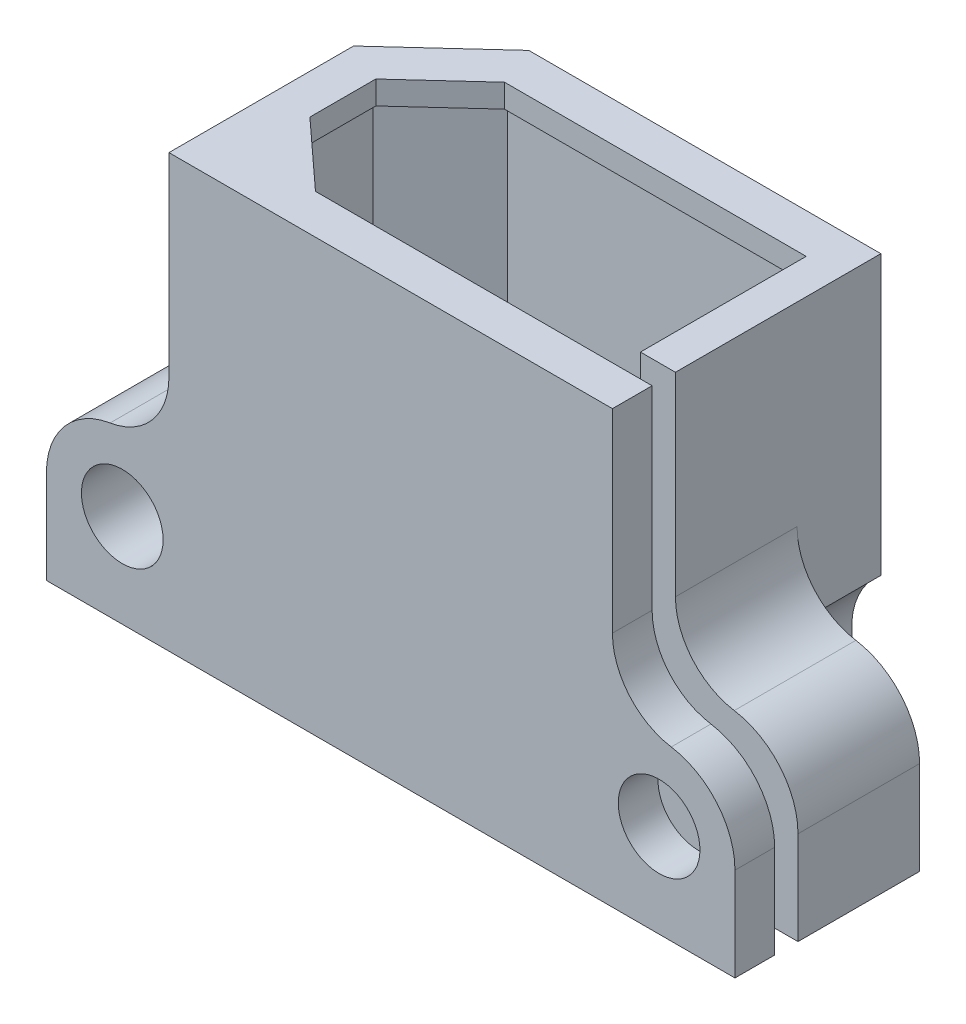
SolidWorks part; units mm, degrees
ref_plane "Front Plane" through (0, 0, 0) normal (0, 0, 1) x (1, 0, 0)
ref_plane "Top Plane" through (0, 0, 0) normal (0, 1, 0) x (1, 0, 0)
ref_plane "Right Plane" through (0, 0, 0) normal (1, 0, 0) x (0, 0, -1)
sketch "Sketch1" plane through (0, 0, 0) normal (0, 1, 0) x (1, 0, 0)
  line L0 (-5, 4.25) -> (-8, 1.5)
  line L1 (-8, 4.25) -> (8, 4.25)
  line L2 (-8, 4.25) -> (-8, -4.25)
  line L3 (-8, -4.25) -> (8, -4.25)
  line L4 (8, 4.25) -> (8, -4.25)
  line L5 (-8, 4.25) -> (8, -4.25) construction
  line L6 (-8, -4.25) -> (8, 4.25) construction
  line L7 (-8, 0) -> (8, 0) construction
  line L8 (-5, -4.25) -> (-8, -1.5)
  line L9 (-9.5, 2.1599) -> (-5.5835, 5.75)
  line L10 (9.5, 5.75) -> (-9.5, 5.75)
  line L11 (9.5, 5.75) -> (9.5, -5.75)
  line L12 (9.5, -5.75) -> (-9.5, -5.75)
  line L13 (-9.5, 5.75) -> (-9.5, -5.75)
  line L14 (9.5, 5.75) -> (-9.5, -5.75) construction
  line L15 (9.5, -5.75) -> (-9.5, 5.75) construction
  line L16 (-9.5, -2.1599) -> (-5.5835, -5.75)
  point P0 (0, 0)
  point P12 (0, 0)
  dimension "D1" = 8.5
  dimension "D2" = 16
  dimension "D3" = 3
  dimension "D4" = 3
  dimension "D5" = 1.5
  dimension "D6" = 1.5
  dimension "D7" = 1.5
extrude "Boss-Extrude1" add sketch "Sketch1" along normal blind 16.5 contours L3 L16 L12 L11 L10 L9 L1 L4 | L16 L13 L12 L3 L2 | L13 L16 L2 L9 | L9 L2 L0 L1 | L2 L16 L3 L8 | L16 L2 L3 region at (-6.1099, 0, -4.4529) region at (-6.9463, 0, -3.2841) region at (-8.6896, 0, 0) region at (-6.9463, 0, 3.2841) region at (-7.7399, 0, 4.0116) region at (-8.2133, 0, 4.5757)
sketch "Sketch7" plane through (0, 16.5, 0) normal (0, 1, 0) x (1, 0, 0)
  line L5 (-5.5835, 5.75) -> (-9.5, 2.1599)
  line L6 (-9.5, 2.1599) -> (-9.5, -5.75)
  line L7 (-9.5, -5.75) -> (9.5, -5.75)
  line L8 (9.5, -5.75) -> (9.5, 5.75)
  line L9 (9.5, 5.75) -> (-5.5835, 5.75)
  line L10 (-5.5835, 5.75) -> (-9.5, 2.1599)
  line L11 (-9.5, 2.1599) -> (-9.5, -5.75)
  line L12 (-9.5, -5.75) -> (9.5, -5.75)
  line L13 (9.5, -5.75) -> (9.5, 5.75)
  line L14 (9.5, 5.75) -> (-5.5835, 5.75)
  line L24 (7.8, 4.05) -> (8, 4.05)
  line L25 (8, 4.25) -> (8, -4.25) construction
  line L26 (7.8, -4.05) -> (8, -4.05)
  line L27 (8, 4.05) -> (8, -4.05)
  line L30 (-7.8, 1.412) -> (-7.8, -1.412)
  line L31 (-7.8, -1.412) -> (-4.9222, -4.05)
  line L32 (-4.9222, -4.05) -> (7.8, -4.05)
  line L33 (7.8, -4.05) -> (7.8, 4.05)
  line L34 (7.8, 4.05) -> (-4.9222, 4.05)
  line L35 (-4.9222, 4.05) -> (-7.8, 1.412)
  line L36 (-7.8, 1.412) -> (-7.8, -1.412)
  line L37 (-7.8, -1.412) -> (-4.9222, -4.05)
  line L38 (-4.9222, -4.05) -> (7.8, -4.05)
  line L39 (7.8, -4.05) -> (7.8, 4.05)
  line L40 (7.8, 4.05) -> (-4.9222, 4.05)
  line L41 (-4.9222, 4.05) -> (-7.8, 1.412)
  line M12 (-5, -4.25) -> (-8, -1.5)
  line M13 (-8, -1.5) -> (-8, 1.5)
  line M14 (-8, 1.5) -> (-5, 4.25)
  line M15 (-5, 4.25) -> (8, 4.25)
  line M16 (8, 4.25) -> (8, -4.25)
  line M17 (8, -4.25) -> (-5, -4.25)
  line M18 (-5.5835, 5.75) -> (-9.5, 2.1599)
  line M19 (-9.5, 2.1599) -> (-9.5, -5.75)
  line M20 (-9.5, -5.75) -> (9.5, -5.75)
  line M21 (9.5, -5.75) -> (9.5, 5.75)
  line M22 (9.5, 5.75) -> (-5.5835, 5.75)
  dimension "D1" = 0
  dimension "D2" = 0.2
extrude "Boss-Extrude7" add sketch "Sketch7" along normal blind 1 contours M22 M18 M19 M20 M21 M17 M12 M13 M14 M15 M16 | L41 L40 L24 L26 L38 L37 L36 M16 M15 M14 M13 M12 M17 region at (1.9583, 16.5, -5.5279) region at (1.4389, 16.5, -4.2312)
sketch "Sketch8" plane through (0, 0, 0) normal (0, -1, 0) x (1, 0, 0)
  line L5 (8, 4.05) -> (-4.9222, 4.05)
  line L6 (-4.9222, 4.05) -> (-7.8, 1.412)
  line L7 (-7.8, 1.412) -> (-7.8, -1.412)
  line L8 (-7.8, -1.412) -> (-4.9222, -4.05)
  line L9 (-4.9222, -4.05) -> (8, -4.05)
  line L10 (-9.5, -2.1599) -> (-5.5835, -5.75)
  line L11 (-5.5835, -5.75) -> (9.5, -5.75)
  line L12 (9.5, -5.75) -> (9.5, 5.75)
  line L13 (9.5, 5.75) -> (-9.5, 5.75)
  line L14 (-9.5, 5.75) -> (-9.5, -2.1599)
  line L16 (-9.5, -2.1599) -> (-5.5835, -5.75)
  line L17 (-5.5835, -5.75) -> (9.5, -5.75)
  line L18 (9.5, -5.75) -> (9.5, 5.75)
  line L19 (9.5, 5.75) -> (-9.5, 5.75)
  line L20 (-9.5, 5.75) -> (-9.5, -2.1599)
  line L21 (8, -4.05) -> (8, 4.05)
  dimension "D1" = 0
extrude "Boss-Extrude8" add sketch "Sketch8" along normal blind 1
sketch "Sketch9" plane through (0, 0, 5.75) normal (0, 0, 1) x (1, 0, 0)
  line L0 (-9.5, 3) -> (9.5, 3) construction
  line L3 (0, 17.5) -> (0, -1) construction
  line L6 (9.5, -1) -> (-9.5, -1) construction
  line L7 (-9.5, 17.5) -> (9.5, 17.5) construction
  line L8 (-9.5, 17.5) -> (-9.5, -1)
  line L9 (9.5, 17.5) -> (9.5, -1)
  line L10 (-9.5, 17.5) -> (-9.5, -1) construction
  line L11 (-9.5, -1) -> (-14.75, -1)
  line L12 (-14.75, -1) -> (-14.75, 3)
  line L13 (9.5, -1) -> (14.75, -1)
  line L14 (14.75, -1) -> (14.75, 3)
  circle A0 centre (-11.5, 3) radius 1.75
  circle A1 centre (-11.5, 3) radius 3.25
  circle A2 centre (11.5, 3) radius 3.25
  circle A3 centre (11.5, 3) radius 1.75
  line M1 (-9.5, 17.5) -> (-9.5, -1)
  line M3 (9.5, -1) -> (9.5, 17.5)
  dimension "D1" = 3.5
  dimension "D3" = 1.5
  dimension "D2" = 23
  dimension "D4" = 4
extrude "Boss-Extrude9" add sketch "Sketch9" against normal up to vertex (7.9099 mm away) contours L8 A1 A0 | A2 L9 A3 | A1 L12 L11 M1 | L14 A2 L13 M3 region at (-9.5836, 3, 5.75) region at (-12.6324, -0.2112, 5.75) region at (12.8886, 5.8457, 5.75) region at (12.6324, -0.2112, 5.75) up to point (-9.5, 17.5, -2.1599)
sketch "Sketch11" plane through (0, 0, -5.75) normal (0, 0, -1) x (-1, 0, 0)
  circle A0 centre (-11.5, 3) radius 3.25
  circle A1 centre (11.5, 3) radius 3.25
  arc A3 (-9.5, 5.5617) -> (-14.75, 3) centre (-11.5, 3) ccw construction
extrude "Cut-Extrude2" cut sketch "Sketch11" against normal up to surface (3.5901 mm away) up to face at (11.6688, 1.2302, -2.1599)
sketch "Sketch12" plane through (0, 17.5, 0) normal (0, 1, 0) x (1, 0, 0)
  line L0 (14.75, 2.1599) -> (9.5, 2.1599) construction
  line L1 (8, -4.05) -> (14.75, -4.05)
  line L2 (8, -4.05) -> (8, -3.05)
  line L3 (8, -3.05) -> (14.75, -3.05)
  line L4 (14.75, -4.05) -> (14.75, -3.05)
  line L7 (14.75, 2.1599) -> (9.5, 2.1599)
  line L8 (9.5, -5.75) -> (14.75, -5.75) construction
  line L9 (9.5, -5.75) -> (14.75, -5.75)
  line L10 (14.75, 2.1599) -> (14.75, -5.75) construction
  line M17 (8, 4.05) -> (8, -4.05)
  line M26 (9.5, -5.75) -> (9.5, 5.75)
  dimension "D1" = 1
extrude "Cut-Extrude3" cut sketch "Sketch12" against normal up to surface (18.5 mm away) contours L1 L4 L3 M26 | L3 L1 M17 M26 region at (8.75, 17.5, 3.55) region at (12.125, 17.5, 3.55) up to face at (0.1614, -1, -1.3043)
fillet "Fillet1" radius 3 3 edges
